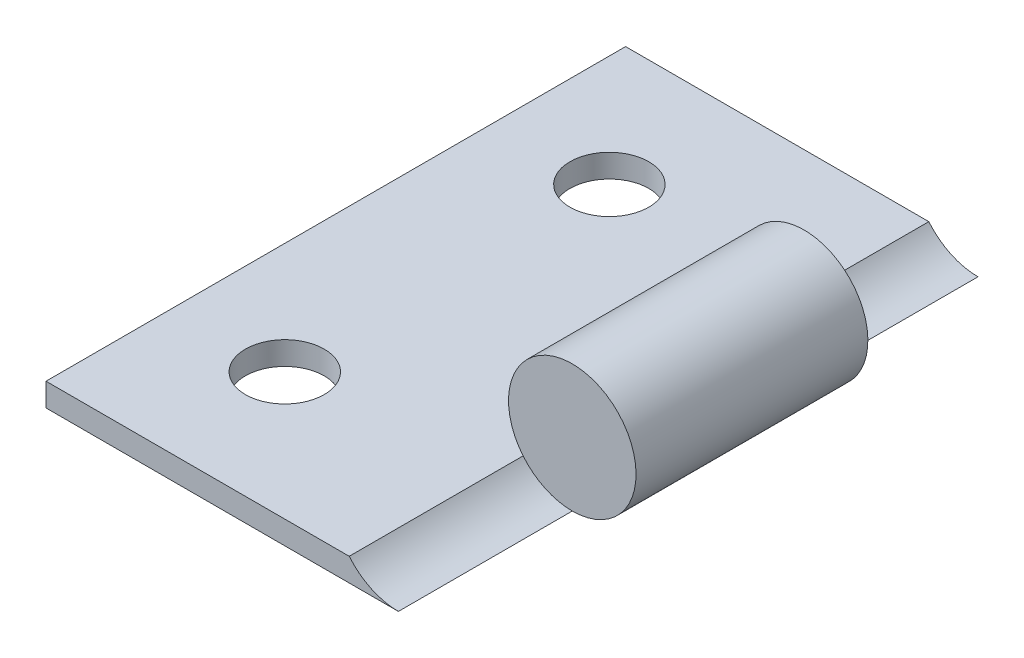
SolidWorks part; units mm, degrees
material "AISI 304"
ref_plane "前视基准面" through (0, 0, 0) normal (0, 0, 1) x (1, 0, 0)
ref_plane "上视基准面" through (0, 0, 0) normal (0, 1, 0) x (1, 0, 0)
ref_plane "右视基准面" through (0, 0, 0) normal (1, 0, 0) x (0, 0, -1)
sketch "草图1" plane through (0, 0, 0) normal (0, 0, 1) x (1, 0, 0)
  line L0 (0, 0) -> (-12.3968, 0) construction
  line L1 (0, 7.4382) -> (0, -11.9267) construction
  line L2 (0, -2.75) -> (-15.2, -2.75)
  line L3 (-15.2, -2.75) -> (-15.2, -1.75)
  line L4 (-15.2, -1.75) -> (-2.1213, -1.75)
  arc A0 (0, -2.75) -> (-2.1213, -1.75) centre (0, 0) ccw
  dimension "D2" = 5.5
  dimension "D1" = 1
  dimension "D3" = 15.2
extrude "凸台-拉伸1" add sketch "草图1" along normal blind 25
sketch "草图2" plane through (0, -1.75, 0) normal (0, 1, 0) x (1, 0, 0)
  line L0 (-15.2, -12.5) -> (7.5492, -12.5) construction
  line L1 (-15.2, -25) -> (-15.2, 0) construction
  circle A0 centre (-10.4, -5.5) radius 1.7
  circle A1 centre (-10.4, -19.5) radius 1.7
  dimension "D3" = 3.4
  dimension "D1" = 14
  dimension "D2" = 10.4
extrude "切除-拉伸1" cut sketch "草图2" against normal blind 25
sketch "草图3" plane through (0, 0, 0) normal (0, 0, -1) x (-1, 0, 0)
  circle A0 centre (0, 0) radius 2.75
extrude "切除-拉伸2" cut sketch "草图3" against normal blind 7.5
extrude "切除-拉伸3" cut sketch "草图3<2>" along normal blind 7.5 from surface starting at face at (-7.572, -1.0656, 25)
sketch "草图3<2>" plane through (0, 0, 0) normal (0, 0, -1) x (-1, 0, 0) same geometry as "草图3"
